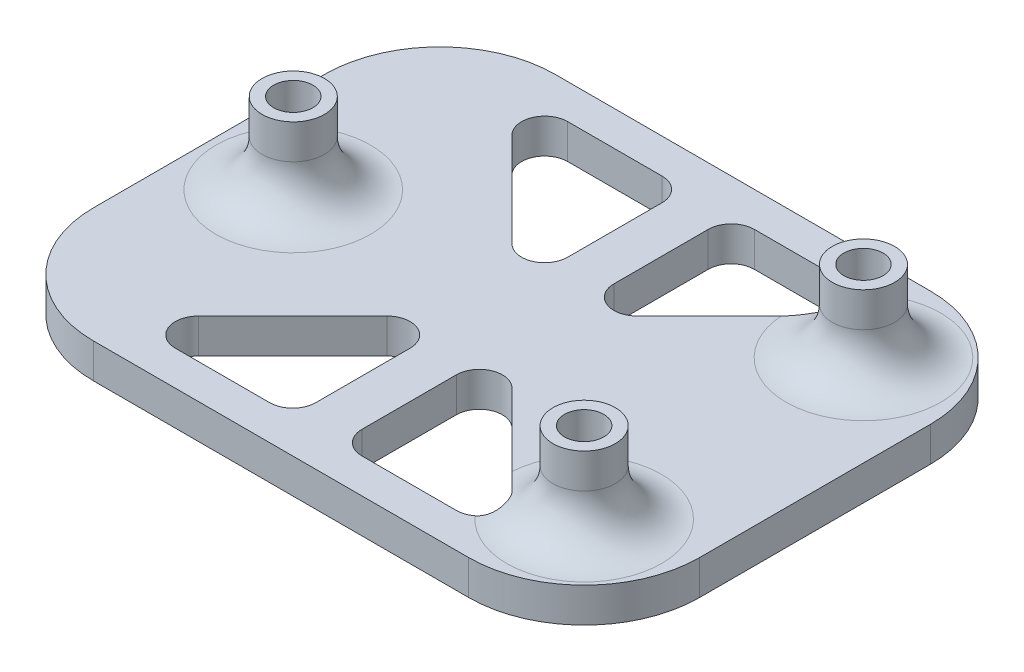
SolidWorks part; units mm, degrees
ref_plane "Front Plane" through (0, 0, 0) normal (0, 0, 1) x (1, 0, 0)
ref_plane "Top Plane" through (0, 0, 0) normal (0, 1, 0) x (1, 0, 0)
ref_plane "Right Plane" through (0, 0, 0) normal (1, 0, 0) x (0, 0, -1)
sketch "Sketch1" plane through (0, 0, 0) normal (0, 1, 0) x (1, 0, 0)
  line L0 (0, 0) -> (0, 20) construction
  line L1 (-26.25, 20) -> (26.25, 20)
  line L2 (-26.25, 20) -> (-26.25, -20)
  line L3 (-26.25, -20) -> (26.25, -20)
  line L4 (26.25, 20) -> (26.25, -20)
  line L5 (0, 0) -> (26.25, 0) construction
  line L6 (-21.25, 15) -> (-21.25, -15) construction
  line L7 (-21.25, -15) -> (21.25, -15) construction
  line L8 (21.25, -15) -> (21.25, 15) construction
  line L9 (21.25, 15) -> (-21.25, 15) construction
  dimension "D1" = 52.5
  dimension "D2" = 40
  dimension "D3" = 42.5
  dimension "D4" = 30
  dimension "D5" = 5
  dimension "D6" = 5
extrude "Boss-Extrude1" add sketch "Sketch1" along normal blind 3
sketch "Sketch2" plane through (0, 3, 0) normal (0, 1, 0) x (1, 0, 0)
  line L0 (0, 0) -> (26.25, 0) construction
  line L1 (21.25, -15) -> (21.25, 15) construction
  line L2 (21.25, 15) -> (-21.25, 15) construction
  line L4 (-21.25, -15) -> (21.25, -15) construction
  line L5 (-21.25, 15) -> (-21.25, -15) construction
  circle A0 centre (-18.95, 0) radius 1.7
  circle A1 centre (18.35, 12.1) radius 1.7
  circle A2 centre (18.35, -12.1) radius 1.7
  dimension "D1" = 3.4
  dimension "D6" = 2.3
  dimension "D2" = 2.9
  dimension "D3" = 2.9
  dimension "D4" = 2.9
  dimension "D5" = 2.9
extrude "Cut-Extrude1" cut sketch "Sketch2" against normal through all
sketch "Sketch3" plane through (0, 3, 0) normal (0, 1, 0) x (1, 0, 0)
  circle A0 centre (-18.95, 0) radius 1.7
  circle A1 centre (-18.95, 0) radius 2.7
  circle A2 centre (18.35, 12.1) radius 1.7
  circle A3 centre (18.35, 12.1) radius 2.7
  circle A4 centre (18.35, -12.1) radius 1.7
  circle A5 centre (18.35, -12.1) radius 2.7
  circle A6 centre (18.35, -12.1) radius 1.7 construction
  circle A7 centre (-18.95, 0) radius 1.7 construction
  circle A8 centre (18.35, 12.1) radius 1.7 construction
  dimension "D1" = 1
extrude "Boss-Extrude2" add sketch "Sketch3" along normal blind 7
fillet "Fillet1" radius 4 3 edges at (18.35, 3, -9.4) (18.35, 3, 14.8) (-18.95, 3, 2.7)
sketch "Sketch4" plane through (0, 3, 0) normal (0, 1, 0) x (1, 0, 0)
  line L0 (-17, 17) -> (-2, 17)
  line L1 (-2, 17) -> (-2, 2)
  line L2 (-2, 2) -> (-17, 17)
  line L3 (2, 17) -> (17, 17)
  line L4 (17, 17) -> (2, 2)
  line L5 (2, 2) -> (2, 17)
  line L6 (0, 0) -> (0, 20) construction
  line L7 (-26.25, 20) -> (26.25, 20) construction
  line L8 (0, 0) -> (-26.25, 0) construction
  line L9 (-26.25, 20) -> (-26.25, -20) construction
  line L10 (2, -2) -> (2, -17)
  line L11 (17, -17) -> (2, -2)
  line L12 (2, -17) -> (17, -17)
  line L13 (-2, -2) -> (-17, -17)
  line L14 (-2, -17) -> (-2, -2)
  line L15 (-17, -17) -> (-2, -17)
  dimension "D1" = 2
  dimension "D2" = 2
  dimension "D3" = 15
  dimension "D4" = 3
extrude "Cut-Extrude2" cut sketch "Sketch4" against normal through all both and the other way through all
fillet "Fillet2" radius 2 12 edges at (17, 1.6708, -17) (2, 1.5, -17) (2, 1.5, -2) (-17, 1.5, -17) (-2, 1.5, -17) (-2, 1.5, -2) (2, 1.5, 17) (17, 1.6708, 17) (2, 1.5, 2) (-2, 1.5, 17) (-17, 1.5, 17) (-2, 1.5, 2)
fillet "Fillet3" radius 10 4 edges at (-26.25, 1.5, 20) (26.25, 1.5, 20) (26.25, 1.5, -20) (-26.25, 1.5, -20)
sketch "Sketch5" plane through (0, 0, 0) normal (0, -1, 0) x (1, 0, 0)
  line L0 (21.25, -15) -> (-21.25, -15) construction
  line L1 (-17.3334, -2.8) -> (-15.7168, 0)
  line L2 (-15.7168, 0) -> (-17.3334, 2.8)
  line L3 (-17.3334, 2.8) -> (-20.5666, 2.8)
  line L4 (-20.5666, 2.8) -> (-22.1832, 0)
  line L5 (-22.1832, 0) -> (-20.5666, -2.8)
  line L6 (-20.5666, -2.8) -> (-17.3334, -2.8)
  line L7 (-26.25, -20) -> (26.25, -20) construction
  line L8 (19.9666, 9.3) -> (21.5832, 12.1)
  line L9 (21.5832, 12.1) -> (19.9666, 14.9)
  line L10 (19.9666, 14.9) -> (16.7334, 14.9)
  line L11 (16.7334, 14.9) -> (15.1168, 12.1)
  line L12 (15.1168, 12.1) -> (16.7334, 9.3)
  line L13 (16.7334, 9.3) -> (19.9666, 9.3)
  line L14 (19.9666, -14.9) -> (21.5832, -12.1)
  line L15 (21.5832, -12.1) -> (19.9666, -9.3)
  line L16 (19.9666, -9.3) -> (16.7334, -9.3)
  line L17 (16.7334, -9.3) -> (15.1168, -12.1)
  line L18 (15.1168, -12.1) -> (16.7334, -14.9)
  line L19 (16.7334, -14.9) -> (19.9666, -14.9)
  circle A0 centre (-18.95, 0) radius 2.8 construction
  circle A1 centre (18.35, 12.1) radius 2.8 construction
  circle A2 centre (18.35, -12.1) radius 2.8 construction
  dimension "D1" = 5.6
extrude "Cut-Extrude3" cut sketch "Sketch5" against normal blind 3.3
